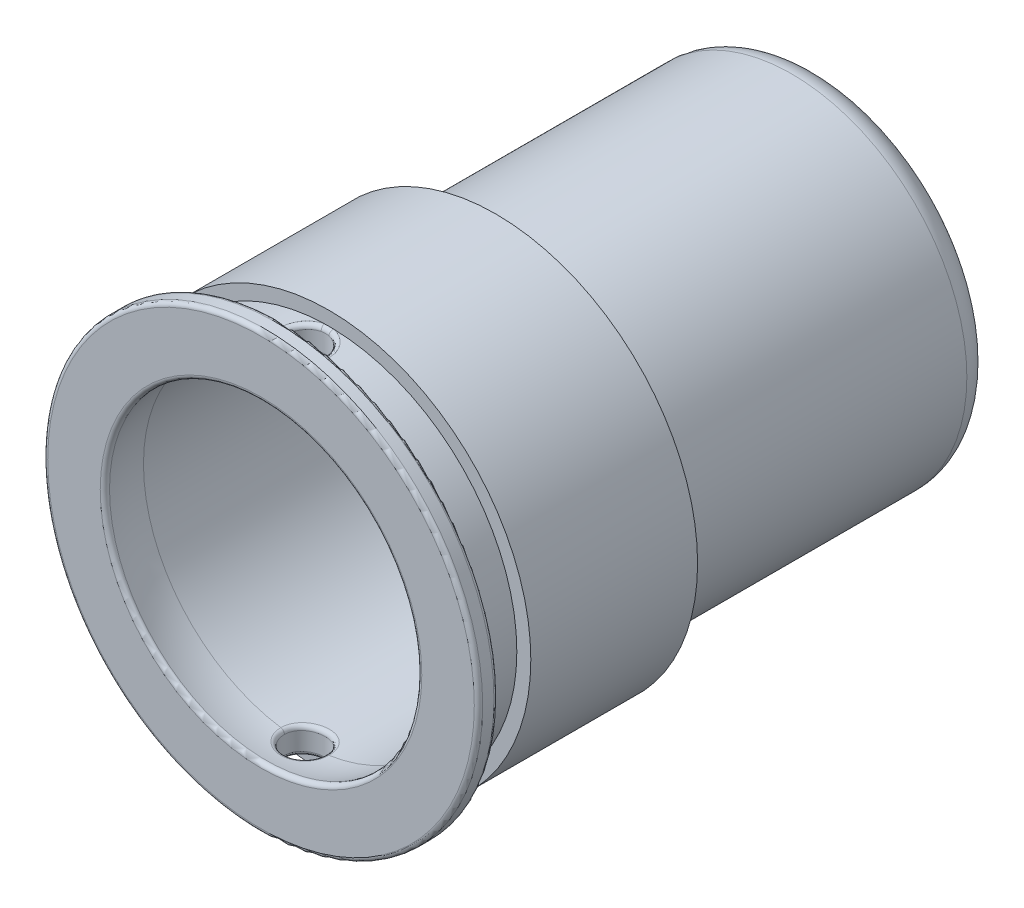
SolidWorks part; units mm, degrees
ref_plane "Front Plane" through (0, 0, 0) normal (0, 0, 1) x (1, 0, 0)
ref_plane "Top Plane" through (0, 0, 0) normal (0, 1, 0) x (1, 0, 0)
ref_plane "Right Plane" through (0, 0, 0) normal (1, 0, 0) x (0, 0, -1)
sketch "Sketch1" plane through (0, 0, 0) normal (0, 0, 1) x (1, 0, 0)
  circle A0 centre (0, 0) radius 9.525
  dimension "D1" = 19.05
extrude "Extrude1" add sketch "Sketch1" along normal blind 10.16
cosmetic thread "Cosmetic Thread1" parameters "D2"=17.7292
sketch "Sketch2" plane through (0, 0, 10.16) normal (0, 0, 1) x (1, 0, 0)
  circle A0 centre (0, 0) radius 10.2679
  dimension "D1" = 20.5359
extrude "Extrude2" add sketch "Sketch2" along normal blind 0.9271
sketch "Sketch3" plane through (0, 0, 10.16) normal (0, 0, -1) x (-1, 0, 0)
  circle A0 centre (0, 0) radius 8.8646
  circle A1 centre (0, 0) radius 9.525 construction
  circle A2 centre (0, 0) radius 9.525
  dimension "D1" = 17.7292
extrude "Extrude3" cut sketch "Sketch3" along normal blind 2.286
sketch "Sketch4" plane through (0, 0, 0) normal (0, 0, -1) x (-1, 0, 0)
  circle A0 centre (0, 0) radius 8.2677
  dimension "D1" = 16.5354
extrude "Extrude4" add sketch "Sketch4" along normal offset from surface (15.24 mm away) 25.4 up to face at (10.2679, 0, 10.16) offset beyond the face yes
sketch "Sketch5" plane through (0, 0, -15.24) normal (0, 0, -1) x (-1, 0, 0)
  circle A0 centre (0, 0) radius 6.9342
  dimension "D1" = 13.8684
fillet "Fillet1" radius 1.27 1 edges at (8.2677, 0, -15.24)
sketch "Sketch6" plane through (0, 0, 11.0871) normal (0, 0, 1) x (1, 0, 0)
  circle A0 centre (0, 0) radius 7.3025
  dimension "D1" = 14.605
extrude "Extrude7" cut sketch "Sketch6" against normal up to surface (0.9271 mm away) up to face at (10.2679, 0, 10.16)
sketch "Sketch7" plane through (0, 0, 0) normal (0, 1, 0) x (1, 0, 0)
  line L0 (0, -10.16) -> (0, -7.874) construction
  line L1 (-8.8646, -7.874) -> (8.8646, -7.874) construction
  line L2 (-8.8646, -7.874) -> (8.8646, -7.874) construction
  line L3 (8.8646, -10.16) -> (-8.8646, -10.16) construction
  line L4 (8.8646, -10.16) -> (-8.8646, -10.16) construction
  circle A0 centre (0, -9.017) radius 0.9652
  dimension "D1" = 1.9304
extrude "Extrude8" cut sketch "Sketch7" against normal through all and the other way through all
sketch "Sketch9" plane through (0, 0, 0) normal (0, 1, 0) x (1, 0, 0)
  line L0 (0, -16.637) -> (0, -1.397)
  arc A0 (0, -16.637) -> (0, -1.397) centre (0, -9.017) ccw
  dimension "D1" = 15.24
sketch "Sketch10" plane through (0, 0, 0) normal (0, 1, 0) x (1, 0, 0)
  line L0 (0, 0) -> (0, -27.2638) construction
revolve "Cut-Revolve6" cut sketch "Sketch9" angle 360 about L0
sketch "Sketch12" plane through (0, 0, -15.24) normal (0, 0, -1) x (-1, 0, 0)
  circle A0 centre (0, 0) radius 7.62
  dimension "D1" = 15.24
extrude "Extrude10" cut sketch "Sketch12" against normal up to next from offset 0.6477 offset against normal yes
extrude "Extrude11" cut sketch "Sketch5" against normal up to next
fillet "Fillet4" radius 0.635 1 edges at (-7.62, 0, -14.5923)
fillet "Fillet5" radius 0.1984 4 edges at (7.3334, 0, 11.0871) (10.2679, 0, 11.0871) (-8.8646, 0, 10.16) (10.2679, 0, 10.16)
fillet "Fillet6" radius 0.1984 8 edges at (0.215, 7.617, 8.076) (-0.1089, -7.6192, 8.058) (0, 7.5586, 9.9822) (0, -7.5586, 9.9822) (0.107, -8.864, 8.0577) (-0.107, 8.864, 8.0577) (-0.107, 8.864, 8.0577) (0.107, -8.864, 8.0577)
fillet "Fillet7" radius 0.1984 2 edges at (-6.9342, 0, -14.5923) (-6.9342, 0, -15.24)
